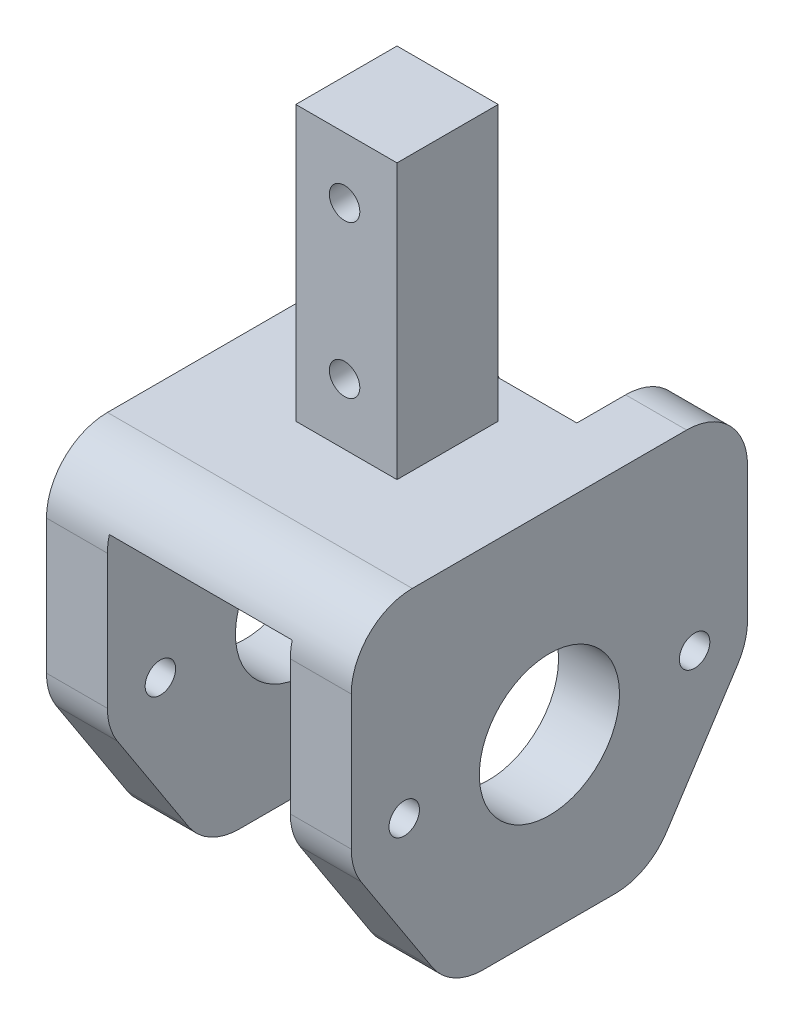
SolidWorks part; units mm, degrees
material "Nylon - impressão"
ref_plane "Plano frontal" through (0, 0, 0) normal (0, 0, 1) x (1, 0, 0)
ref_plane "Plano superior" through (0, 0, 0) normal (0, 1, 0) x (1, 0, 0)
ref_plane "Plano direito" through (0, 0, 0) normal (1, 0, 0) x (0, 0, -1)
sketch "Esboço1" plane through (0, 0, 0) normal (0, 1, 0) x (1, 0, 0)
  line L1 (-8.3, -8.3) -> (8.3, -8.3)
  line L2 (-8.3, -8.3) -> (-8.3, 8.3)
  line L3 (-8.3, 8.3) -> (8.3, 8.3)
  line L4 (8.3, -8.3) -> (8.3, 8.3)
  line L5 (-8.3, -8.3) -> (8.3, 8.3) construction
  line L6 (-8.3, 8.3) -> (8.3, -8.3) construction
  point P0 (0, 0)
  dimension "D1" = 16.6
extrude "Ressalto-extrusão1" add sketch "Esboço1" along normal blind 45
sketch "Esboço2" plane through (0, 0, 0) normal (0, -1, 0) x (1, 0, 0)
  line L1 (-25, -32.5) -> (25, -32.5)
  line L2 (-25, -32.5) -> (-25, 32.5)
  line L3 (-25, 32.5) -> (25, 32.5)
  line L4 (25, -32.5) -> (25, 32.5)
  line L5 (-25, -32.5) -> (25, 32.5) construction
  line L6 (-25, 32.5) -> (25, -32.5) construction
  point P0 (0, 0)
  dimension "D1" = 65
  dimension "D2" = 50
extrude "Ressalto-extrusão2" add sketch "Esboço2" along normal blind 60
sketch "Esboço3" plane through (0, 0, 32.5) normal (0, 0, 1) x (1, 0, 0)
  line L0 (25, -60) -> (-25, -60) construction
  line L1 (-15, -60) -> (15, -60)
  line L2 (-15, -60) -> (-15, -7.5)
  line L3 (-15, -7.5) -> (15, -7.5)
  line L4 (15, -60) -> (15, -7.5)
  line L5 (-25, -60) -> (-25, 0) construction
  line L6 (25, 0) -> (-25, 0) construction
  line L7 (25, -60) -> (25, 0) construction
  dimension "D1" = 10
  dimension "D2" = 7.5
  dimension "D3" = 10
extrude "Corte-extrusão1" cut sketch "Esboço3" against normal through all
sketch "Esboço4" plane through (25, 0, 0) normal (1, 0, 0) x (0, 0, -1)
  line L0 (32.5, -60) -> (-32.5, -60) construction
  line L1 (32.5, -60) -> (32.5, 0) construction
  circle A3 centre (0, -32) radius 11.5
  circle A10 centre (-23.8125, -32) radius 2.5
  circle A13 centre (23.8125, -32) radius 2.5
  circle A16 centre (0, -32) radius 23.8125 construction
  arc A17 (-9.4071, -11.4434) -> (-11.8406, -13.8769) centre (-11.9062, -11.3778) ccw [skipped]
  arc A18 (11.8464, -13.8771) -> (13.5071, -13.298) centre (11.9063, -11.3778) ccw [skipped]
  arc A20 (-11.8406, -55.1214) -> (-14.4054, -52.5566) centre (-11.9062, -52.6222) ccw [skipped]
  arc A21 (11.8345, -55.1212) -> (10.2346, -54.4811) centre (11.9063, -52.6222) ccw [skipped]
  point P21 (0, -32)
  point P22 (0, -32)
  dimension "D2" = 47.625
  dimension "D4" = 5
  dimension "D5" = 23
  dimension "D1" = 28
  dimension "D3" = 32.5
  dimension "D6" = 6
extrude "Corte-extrusão2" cut sketch "Esboço4" against normal through all
sketch "Esboço5" plane through (-25, 0, 0) normal (-1, 0, 0) x (0, 0, 1)
  line L0 (0, 0) -> (0, -9.2798) construction
  line L1 (32.5, 0) -> (-32.5, 0) construction
  line L3 (-14.5, -11) -> (-14.5, 0)
  line L4 (-14.5, 0) -> (-32.5, 0)
  line L5 (-32.5, 0) -> (-32.5, -11)
  line L6 (-32.5, -60) -> (-32.5, 0) construction
  line L7 (-32.5, -11) -> (-14.5, -11)
  dimension "D1" = 18
  dimension "D2" = 11
extrude "Corte-extrusão3" cut sketch "Esboço5" against normal blind 40
chamfer "Chanfro1" distance 25 angle 33 4 edges at (-20, -60, -32.5) (-20, -60, 32.5) (20, -60, 32.5) (20, -60, -32.5) first distance on face at (-20, -35.5, -32.5) first distance on face at (0, -31.875, 32.5) first distance on face at (20, -30, -32.5)
fillet "Filete2" radius 10 11 edges at (20, 0, -32.5) (20, -35, -32.5) (20, -60, 16.2648) (20, -60, -16.2648) (20, -35, 32.5) (0, 0, 32.5) (-20, -60, -16.2648) (-20, -60, 16.2648) (-20, -35, 32.5) (-20, -35, -32.5) (-20, -11, -32.5)
sketch "Esboço6" plane through (0, 0, 8.3) normal (0, 0, 1) x (1, 0, 0)
  circle A2 centre (-0.3, 10) radius 2.5
  circle A3 centre (-0.3, 35) radius 2.5
extrude "Corte-extrusão4" cut sketch "Esboço6" against normal through all
